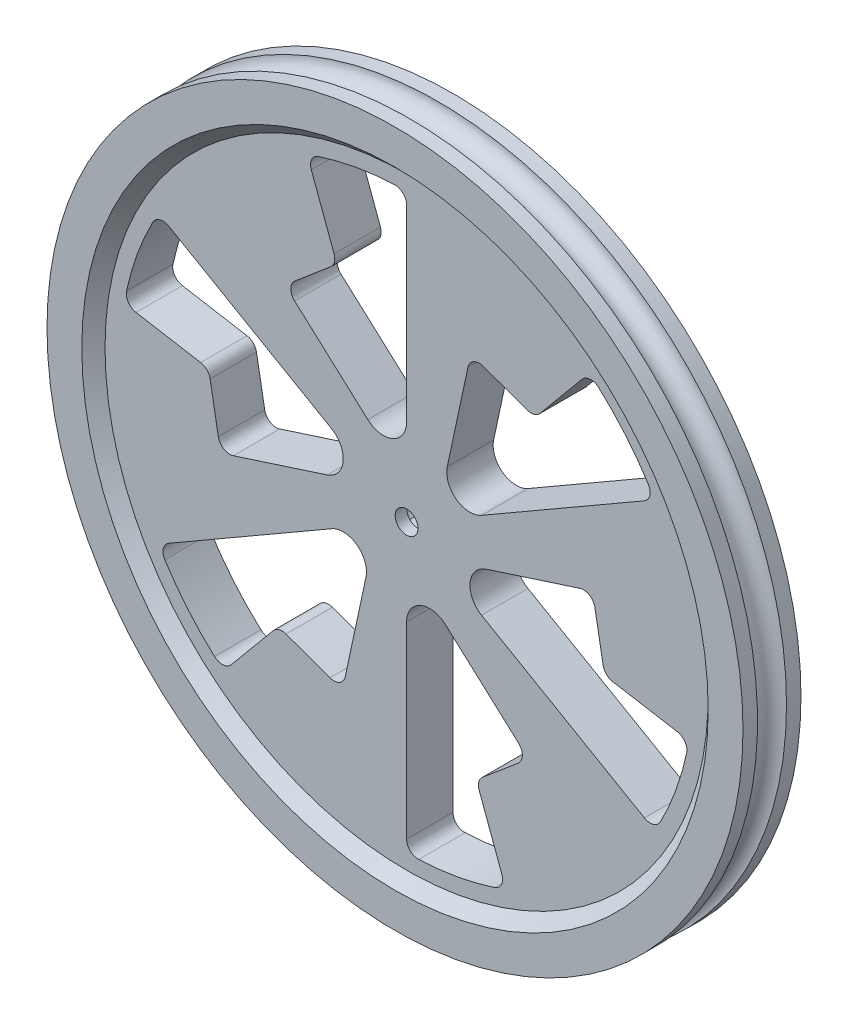
SolidWorks part; units mm, degrees
ref_plane "Front Plane" through (0, 0, 0) normal (0, 0, 1) x (1, 0, 0)
ref_plane "Top Plane" through (0, 0, 0) normal (0, 1, 0) x (1, 0, 0)
ref_plane "Right Plane" through (0, 0, 0) normal (1, 0, 0) x (0, 0, -1)
sketch "Sketch1" plane through (0, 0, 0) normal (0, 0, 1) x (1, 0, 0)
  line L0 (0, 3.7536) -> (0, 31.3564)
  line L2 (20.0252, 24.1291) -> (14.0413, 16.9189)
  line L3 (14.0413, 16.9189) -> (7.0206, 19.4527)
  line L4 (7.0206, 19.4527) -> (3.2507, 1.8768)
  line L7 (3.2507, 1.8768) -> (27.1555, 15.6782)
  line L9 (20.3568, 3.6463) -> (3.2507, -1.8768)
  line L10 (21.6728, -3.7007) -> (20.3568, 3.6463)
  line L12 (3.2507, -1.8768) -> (27.1555, -15.6782)
  line L14 (13.3362, -15.8064) -> (0, -3.7536)
  line L15 (7.6315, -20.6195) -> (13.3362, -15.8064)
  line L17 (0, -3.7536) -> (0, -31.3564)
  line L19 (-7.0206, -19.4527) -> (-3.2507, -1.8768)
  line L20 (-14.0413, -16.9189) -> (-7.0206, -19.4527)
  line L22 (-3.2507, -1.8768) -> (-27.1555, -15.6782)
  line L24 (-20.3568, -3.6463) -> (-3.2507, 1.8768)
  line L25 (-21.6728, 3.7007) -> (-20.3568, -3.6463)
  line L27 (-3.2507, 1.8768) -> (-27.1555, 15.6782)
  line L29 (-13.3362, 15.8064) -> (0, 3.7536)
  line L30 (-7.6315, 20.6195) -> (-13.3362, 15.8064)
  line L31 (-10.8838, 29.4069) -> (-7.6315, 20.6195)
  line L32 (-30.9091, 5.2778) -> (-21.6728, 3.7007)
  line L33 (-14.0413, -16.9189) -> (-20.0252, -24.1291)
  line L34 (7.6315, -20.6195) -> (10.8838, -29.4069)
  line L35 (21.6728, -3.7007) -> (30.9091, -5.2778)
  circle A0 centre (0, 0) radius 38.1
  arc A1 (0, 31.3564) -> (-10.8838, 29.4069) centre (0, 0) ccw
  arc A2 (-27.1555, 15.6782) -> (-30.9091, 5.2778) centre (0, 0) ccw
  arc A3 (-27.1555, -15.6782) -> (-20.0252, -24.1291) centre (0, 0) ccw
  arc A4 (0, -31.3564) -> (10.8838, -29.4069) centre (0, 0) ccw
  arc A5 (27.1555, -15.6782) -> (30.9091, -5.2778) centre (0, 0) ccw
  arc A6 (27.1555, 15.6782) -> (20.0252, 24.1291) centre (0, 0) ccw
  point P36 (0, 0)
  dimension "D1" = 76.2
  dimension "D2" = 6
extrude "Boss-Extrude1" add sketch "Sketch1" along normal blind 6.35
fillet "Fillet1" radius 2.54 6 edges at (-3.2507, -1.8768, 3.175) (0, -3.7536, 3.175) (3.2507, -1.8768, 3.175) (3.2507, 1.8768, 3.175) (0, 3.7536, 3.175) (-3.2507, 1.8768, 3.175)
sketch "Sketch2" plane through (0, 0, 6.35) normal (0, 0, 1) x (1, 0, 0)
  line L1 (-1.9562, 1.905) -> (1.9562, 1.905)
  line L2 (-1.9562, -1.905) -> (1.9562, -1.905)
  line L3 (-1.9562, -1.905) -> (-1.9562, 1.905) construction
  arc A0 (-1.9562, 1.905) -> (-1.9562, -1.905) centre (0, 0) ccw
  arc A1 (1.9562, 1.905) -> (-1.9562, 1.905) centre (0, 0) ccw construction
  arc A2 (-1.9562, -1.905) -> (1.9562, -1.905) centre (0, 0) ccw construction
  arc A3 (1.9562, -1.905) -> (1.9562, 1.905) centre (0, 0) ccw
  dimension "D1" = 5.461
  dimension "D2" = 3.81
extrude "Cut-Extrude1" cut sketch "Sketch2" against normal blind 6.35 from offset 2.54 offset against normal yes
sketch "Sketch3" plane through (0, 0, 0) normal (0, 1, 0) x (1, 0, 0)
  line L0 (-38.1, 0) -> (-38.1, -6.35) construction
  line L1 (38.1, 0) -> (-38.1, 0) construction
  line L2 (0, 0) -> (-34.29, 0)
  line L3 (0, 0) -> (0, -1.27)
  line L4 (0, -1.27) -> (-34.29, -1.27)
  line L5 (-34.29, 0) -> (-34.29, -1.27)
  line L6 (-38.1, -6.35) -> (38.1, -6.35) construction
  line L7 (0, -6.35) -> (-34.29, -6.35)
  line L8 (0, -6.35) -> (0, -5.08)
  line L9 (0, -5.08) -> (-34.29, -5.08)
  line L10 (-34.29, -6.35) -> (-34.29, -5.08)
  line L11 (0, -1.27) -> (0, -5.08)
  line L12 (-34.29, -1.27) -> (-34.29, -5.08)
  circle A0 centre (-38.1, -3.175) radius 1.5875
  dimension "D3" = 3.175
  dimension "D1" = 1.27
  dimension "D2" = 34.29
revolve "Cut-Revolve1" cut sketch "Sketch3" angle 360 about L11 region at (-17.145, 0, 5.715) region at (-38.1, 0, 3.175)
fillet "Fillet2" radius 1.27 24 edges at (-7.0206, -19.4527, 2.54) (-14.0413, -16.9189, 2.54) (-20.0252, -24.1291, 2.54) (-27.1555, -15.6782, 2.54) (0, -31.3564, 2.54) (13.3362, -15.8064, 2.54) (7.6315, -20.6195, 2.54) (10.8838, -29.4069, 2.54) (27.1555, -15.6782, 2.54) (30.9091, -5.2778, 2.54) (21.6728, -3.7007, 2.54) (20.3568, 3.6463, 2.54) (27.1555, 15.6782, 2.54) (20.0252, 24.1291, 2.54) (14.0413, 16.9189, 2.54) (7.0206, 19.4527, 2.54) (0, 31.3564, 2.54) (-13.3362, 15.8064, 2.54) (-7.6315, 20.6195, 2.54) (-10.8838, 29.4069, 2.54) (-27.1555, 15.6782, 2.54) (-20.3568, -3.6463, 2.54) (-21.6728, 3.7007, 2.54) (-30.9091, 5.2778, 2.54)
sketch "Sketch4" plane through (0, 0, 5.08) normal (0, 0, 1) x (1, 0, 0)
  circle A0 centre (0, 0) radius 1.25
  dimension "D1" = 2.5
extrude "Cut-Extrude2" cut sketch "Sketch4" against normal blind 6.35
chamfer "Chamfer1" distance 1.27 angle 45 1 edges at (-34.29, 0, 5.08)
